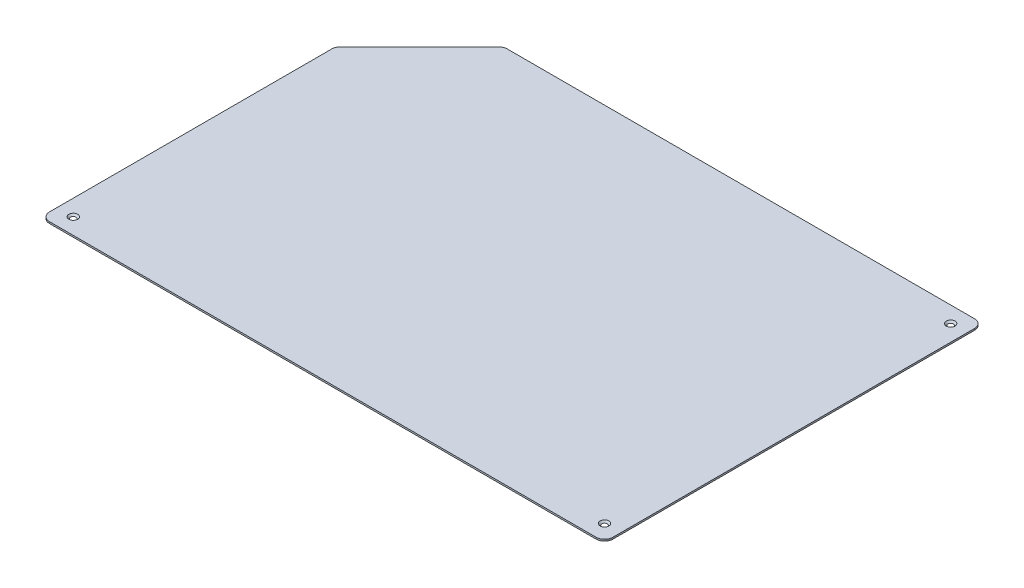
SolidWorks part; units mm, degrees
material "Alumina"
ref_plane "Front Plane" through (0, 0, 0) normal (0, 0, 1) x (1, 0, 0)
ref_plane "Top Plane" through (0, 0, 0) normal (0, 1, 0) x (1, 0, 0)
ref_plane "Right Plane" through (0, 0, 0) normal (1, 0, 0) x (0, 0, -1)
sketch "Sketch1" plane through (0, 0, 0) normal (0, 1, 0) x (1, 0, 0)
  line L1 (-300, -225) -> (300, -225)
  line L2 (-300, -225) -> (-300, 225) construction
  line L3 (-300, 225) -> (300, 225)
  line L4 (300, -225) -> (300, 225)
  line L5 (-300, -225) -> (300, 225) construction
  line L6 (-300, 225) -> (300, -225) construction
  line L7 (-370, -225) -> (-300, -225)
  line L8 (-370, -225) -> (-370, 225)
  line L9 (-370, 225) -> (-300, 225)
  line L10 (-300, -225) -> (-300, 225)
  line L11 (-370, -225) -> (-300, 225) construction
  line L12 (-370, 225) -> (-300, -225) construction
  point P0 (0, 0)
  point P6 (-335, 0)
  dimension "D1" = 450
  dimension "D2" = 600
  dimension "D3" = 70
extrude "Boss-Extrude1" add sketch "Sketch1" along normal blind 2 contours L7 L10 L9 L8 | L10 L1 L4 L3 region at (0, 0, 0) region at (-335, 0, 0)
sketch "Sketch2" plane through (0, 2, 0) normal (0, 1, 0) x (1, 0, 0)
  line L0 (-300, -225) -> (300, -225) construction
  line L1 (300, -225) -> (300, 225) construction
  line L2 (-300, 225) -> (300, 225) construction
  line L3 (-370, 225) -> (-300, 225) construction
  line L4 (-370, -225) -> (-370, 225) construction
  line L6 (-300, -225) -> (300, -225) construction
  line L7 (300, -225) -> (300, 225) construction
  line L8 (-300, 225) -> (300, 225) construction
  line L9 (-370, 225) -> (-300, 225) construction
  line L10 (-370, -225) -> (-370, 225) construction
  line L12 (-370, 225) -> (-350.8076, 205.8076) construction
  line L13 (-350.8076, 205.8076) -> (280.8076, 205.8076) construction
  line L14 (-350.8076, 205.8076) -> (-350.8076, -205.8076) construction
  line L15 (-350.8076, -205.8076) -> (280.8076, -205.8076) construction
  line L16 (280.8076, 205.8076) -> (280.8076, -205.8076) construction
  line L17 (280.8076, 205.8076) -> (300, 225) construction
  line L18 (280.8076, -205.8076) -> (300, -225) construction
  line L19 (-340.8076, 215.8076) -> (35014.5314, 35571.1467) construction
  line L20 (-35, 205.8076) -> (-35, -49794.1924) construction
  line L21 (0, 0) -> (50000, 0) construction
  line L22 (-331.6152, 186.6152) -> (35023.723, -35168.7247) construction
  line L23 (-270, 225) -> (-370, 125) construction
  circle A0 centre (-350.8076, 205.8076) radius 3 construction
  arc A1 (-370, 215) -> (-360, 225) centre (-360, 215) cw construction
  arc A2 (-341.6152, 186.6152) -> (-331.6152, 196.6152) centre (-341.6152, 196.6152) ccw construction
  arc A3 (271.6152, 186.6152) -> (261.6152, 196.6152) centre (271.6152, 196.6152) cw construction
  arc A4 (271.6152, -186.6152) -> (261.6152, -196.6152) centre (271.6152, -196.6152) ccw construction
  arc A5 (-341.6152, 186.6152) -> (-350.8076, 177.4228) centre (-341.6152, 177.4228) ccw construction
  arc A6 (-331.6152, 196.6152) -> (-322.4228, 205.8076) centre (-322.4228, 196.6152) cw construction
  arc A7 (271.6152, 186.6152) -> (280.8076, 177.4228) centre (271.6152, 177.4228) cw construction
  arc A8 (261.6152, 196.6152) -> (252.4228, 205.8076) centre (252.4228, 196.6152) ccw construction
  arc A9 (261.6152, -196.6152) -> (252.4228, -205.8076) centre (252.4228, -196.6152) cw construction
  arc A10 (271.6152, -186.6152) -> (280.8076, -177.4228) centre (271.6152, -177.4228) ccw construction
  circle A11 centre (-350.8076, 172.4767) radius 3 construction
  circle A13 centre (-317.4767, 205.8076) radius 3 construction
  arc A15 (-331.6152, -196.6152) -> (-322.4228, -205.8076) centre (-322.4228, -196.6152) ccw construction
  arc A16 (-341.6152, -186.6152) -> (-331.6152, -196.6152) centre (-341.6152, -196.6152) cw construction
  arc A17 (-341.6152, -186.6152) -> (-350.8076, -177.4228) centre (-341.6152, -177.4228) cw construction
  point P10 (-352.9289, 207.9289)
  point P16 (-367.0711, 222.0711)
  point P27 (-35, 205.8076)
  point P39 (-334.5442, 189.5442)
  point P53 (-350.8076, 175.4767)
  point P56 (-350.8076, 202.8076)
  dimension "D2" = 6
  dimension "D3" = 10
  dimension "D1" = 45
  dimension "D4" = 20
  dimension "D5" = 45
  dimension "D6" = 100
  dimension "D7" = 20
  dimension "D8" = 27.3309
sketch "Sketch6" plane through (0, 2, 0) normal (0, 1, 0) x (1, 0, 0)
  line L0 (280.8076, 177.4228) -> (280.8076, -177.4228) construction
  line L1 (-280, 205.8076) -> (252.4228, 205.8076) construction
  line L2 (-350.8076, 205.8076) -> (280.8076, 205.8076) construction
  line L5 (-350.8076, -205.8076) -> (280.8076, -205.8076) construction
  line L6 (-280, -205.8076) -> (252.4228, -205.8076) construction
  line L7 (-141752.968, 141607.9749) -> (176445.0758, -176590.0843) construction
  line L8 (-341.0607, 198.8891) -> (-332.7279, 190.5564)
  line L9 (-343.8891, 196.0607) -> (-341.0607, 198.8891) construction
  line L10 (-350.8076, 172.4767) -> (-317.4767, 205.8076) construction
  line L11 (-350.8076, 205.8076) -> (-334.1421, 189.1421) construction
  line L12 (-343.8891, 196.0607) -> (-335.5564, 187.7279)
  line L13 (-283.4499, 201.8076) -> (-67.3575, 201.8076) construction
  line L14 (-280, 205.8076) -> (-280, 201.8076)
  line L16 (-280, 224.1399) -> (-280, -49775.8601) construction
  line L17 (-300, -225) -> (-300, 225) construction
  line L18 (-300, -225) -> (-300, 225) construction
  arc A0 (271.6152, -186.6152) -> (280.8076, -177.4228) centre (271.6152, -177.4228) ccw construction
  arc A1 (271.6152, -186.6152) -> (261.6152, -196.6152) centre (271.6152, -196.6152) ccw construction
  arc A2 (252.4228, -205.8076) -> (261.6152, -196.6152) centre (252.4228, -196.6152) ccw construction
  arc A3 (280.8076, 177.4228) -> (271.6152, 186.6152) centre (271.6152, 177.4228) ccw construction
  arc A4 (261.6152, 196.6152) -> (271.6152, 186.6152) centre (271.6152, 196.6152) ccw construction
  arc A5 (261.6152, 196.6152) -> (252.4228, 205.8076) centre (252.4228, 196.6152) ccw construction
  arc A6 (271.6152, -186.6152) -> (280.8076, -177.4228) centre (271.6152, -177.4228) ccw construction
  arc A7 (271.6152, -186.6152) -> (261.6152, -196.6152) centre (271.6152, -196.6152) ccw construction
  arc A8 (252.4228, -205.8076) -> (261.6152, -196.6152) centre (252.4228, -196.6152) ccw construction
  arc A9 (280.8076, 177.4228) -> (271.6152, 186.6152) centre (271.6152, 177.4228) ccw construction
  arc A10 (261.6152, 196.6152) -> (271.6152, 186.6152) centre (271.6152, 196.6152) ccw construction
  arc A11 (261.6152, 196.6152) -> (252.4228, 205.8076) centre (252.4228, 196.6152) ccw construction
  arc A12 (-298.8275, 194.972) -> (-332.7279, 190.5564) centre (-317.4767, 205.8076) cw
  arc A13 (-335.5564, 187.7279) -> (-295.3689, 192.9625) centre (-317.4767, 205.8076) ccw
  arc A14 (-341.0607, 198.8891) -> (-343.8891, 196.0607) centre (-342.4749, 197.4749) ccw
  arc A15 (-298.8275, 194.972) -> (-280, 205.8076) centre (-280, 184.0329) cw
  arc A16 (-295.3689, 192.9625) -> (-280, 201.8076) centre (-280, 184.0329) cw
  point P31 (-342.4749, 197.4749)
  dimension "D1" = 4
  dimension "D2" = 20
extrude "Cut-Extrude1" cut sketch "Sketch6" against normal blind 1.5
hole_wizard "Tap Drill for M5x0.8 Tap2" positions "3DSketch4" profile "Sketch10" hole size "M5x0.8" standard "ANSI Metric" end condition through all
sketch3d "3DSketch4"
  point P0 (-350.8076, 2, 205.8076)
  point P3 (-350.8076, 2, -205.8076)
  point P6 (-317.4767, 2, -205.8076)
  point P9 (-350.8076, 2, -172.4767)
  point P12 (280.8076, 2, -205.8076)
  point P15 (280.8076, 2, 205.8076)
sketch "Sketch10" plane through (-350.8076, 2, 205.8076) normal (1, 0, 0) x (0, 0, 1)
  line L0 (0, 0) -> (0, 2)
  line L1 (0, 2) -> (2.1, 2)
  line L2 (2.1, 2) -> (2.1, 0)
  line L5 (2.1, 0) -> (0, 0)
  line L11 (0, -6.35) -> (0, 107.95) construction
  dimension "Thru Hole Dia." = 4.2
  dimension "Thru Hole Depth" = 2
sketch "Sketch11" plane through (0, 0, 225) normal (0, 0, 1) x (1, 0, 0)
  line L0 (-280, 2) -> (-298.8275, 2) construction
  line L1 (-280, 2) -> (-298.8275, 2) construction
  line L3 (-280, 2) -> (-280, 1.5)
  line L4 (-280, 2) -> (-278, 2)
  line L5 (-141762.1638, 2) -> (176435.8877, 2) construction
  line L6 (-278, 2) -> (-278, 1.5)
  line L7 (-270, 2) -> (-270, 1.5)
  line L8 (-270, 2) -> (-268, 2)
  line L9 (-268, 2) -> (-268, 1.5)
  line L10 (-260, 2) -> (-260, 1.5)
  line L11 (-260, 2) -> (-258, 2)
  line L12 (-258, 2) -> (-258, 1.5)
  line L13 (-250, 2) -> (-250, 1.5)
  line L14 (-250, 2) -> (-248, 2)
  line L15 (-248, 2) -> (-248, 1.5)
  line L16 (-240, 2) -> (-240, 1.5)
  line L17 (-240, 2) -> (-238, 2)
  line L18 (-238, 2) -> (-238, 1.5)
  line L19 (-230, 2) -> (-230, 1.5)
  line L20 (-230, 2) -> (-228, 2)
  line L21 (-228, 2) -> (-228, 1.5)
  line L22 (-220, 2) -> (-220, 1.5)
  line L23 (-220, 2) -> (-218, 2)
  line L24 (-218, 2) -> (-218, 1.5)
  line L25 (-210, 2) -> (-210, 1.5)
  line L26 (-210, 2) -> (-208, 2)
  line L27 (-208, 2) -> (-208, 1.5)
  line L28 (-200, 2) -> (-200, 1.5)
  line L29 (-200, 2) -> (-198, 2)
  line L30 (-198, 2) -> (-198, 1.5)
  line L31 (-190, 2) -> (-190, 1.5)
  line L32 (-190, 2) -> (-188, 2)
  line L33 (-188, 2) -> (-188, 1.5)
  line L34 (-180, 2) -> (-180, 1.5)
  line L35 (-180, 2) -> (-178, 2)
  line L36 (-178, 2) -> (-178, 1.5)
  line L37 (-170, 2) -> (-170, 1.5)
  line L38 (-170, 2) -> (-168, 2)
  line L39 (-168, 2) -> (-168, 1.5)
  line L40 (-160, 2) -> (-160, 1.5)
  line L41 (-160, 2) -> (-158, 2)
  line L42 (-158, 2) -> (-158, 1.5)
  line L43 (-150, 2) -> (-150, 1.5)
  line L44 (-150, 2) -> (-148, 2)
  line L45 (-148, 2) -> (-148, 1.5)
  line L46 (-140, 2) -> (-140, 1.5)
  line L47 (-140, 2) -> (-138, 2)
  line L48 (-138, 2) -> (-138, 1.5)
  line L49 (-130, 2) -> (-130, 1.5)
  line L50 (-130, 2) -> (-128, 2)
  line L51 (-128, 2) -> (-128, 1.5)
  line L52 (-120, 2) -> (-120, 1.5)
  line L53 (-120, 2) -> (-118, 2)
  line L54 (-118, 2) -> (-118, 1.5)
  line L55 (-110, 2) -> (-110, 1.5)
  line L56 (-110, 2) -> (-108, 2)
  line L57 (-108, 2) -> (-108, 1.5)
  line L58 (-100, 2) -> (-100, 1.5)
  line L59 (-100, 2) -> (-98, 2)
  line L60 (-98, 2) -> (-98, 1.5)
  line L61 (-90, 2) -> (-90, 1.5)
  line L62 (-90, 2) -> (-88, 2)
  line L63 (-88, 2) -> (-88, 1.5)
  line L64 (-80, 2) -> (-80, 1.5)
  line L65 (-80, 2) -> (-78, 2)
  line L66 (-78, 2) -> (-78, 1.5)
  line L67 (-70, 2) -> (-70, 1.5)
  line L68 (-70, 2) -> (-68, 2)
  line L69 (-68, 2) -> (-68, 1.5)
  line L70 (-60, 2) -> (-60, 1.5)
  line L71 (-60, 2) -> (-58, 2)
  line L72 (-58, 2) -> (-58, 1.5)
  line L73 (-50, 2) -> (-50, 1.5)
  line L74 (-50, 2) -> (-48, 2)
  line L75 (-48, 2) -> (-48, 1.5)
  line L76 (-40, 2) -> (-40, 1.5)
  line L77 (-40, 2) -> (-38, 2)
  line L78 (-38, 2) -> (-38, 1.5)
  line L79 (-30, 2) -> (-30, 1.5)
  line L80 (-30, 2) -> (-28, 2)
  line L81 (-28, 2) -> (-28, 1.5)
  line L82 (-20, 2) -> (-20, 1.5)
  line L83 (-20, 2) -> (-18, 2)
  line L84 (-18, 2) -> (-18, 1.5)
  line L85 (-10, 2) -> (-10, 1.5)
  line L86 (-10, 2) -> (-8, 2)
  line L87 (-8, 2) -> (-8, 1.5)
  line L88 (0, 2) -> (0, 1.5)
  line L89 (0, 2) -> (2, 2)
  line L90 (2, 2) -> (2, 1.5)
  line L91 (10, 2) -> (10, 1.5)
  line L92 (10, 2) -> (12, 2)
  line L93 (12, 2) -> (12, 1.5)
  line L94 (20, 2) -> (20, 1.5)
  line L95 (20, 2) -> (22, 2)
  line L96 (22, 2) -> (22, 1.5)
  line L97 (30, 2) -> (30, 1.5)
  line L98 (30, 2) -> (32, 2)
  line L99 (32, 2) -> (32, 1.5)
  line L100 (40, 2) -> (40, 1.5)
  line L101 (40, 2) -> (42, 2)
  line L102 (42, 2) -> (42, 1.5)
  line L103 (50, 2) -> (50, 1.5)
  line L104 (50, 2) -> (52, 2)
  line L105 (52, 2) -> (52, 1.5)
  line L106 (60, 2) -> (60, 1.5)
  line L107 (60, 2) -> (62, 2)
  line L108 (62, 2) -> (62, 1.5)
  line L109 (70, 2) -> (70, 1.5)
  line L110 (70, 2) -> (72, 2)
  line L111 (72, 2) -> (72, 1.5)
  line L112 (80, 2) -> (80, 1.5)
  line L113 (80, 2) -> (82, 2)
  line L114 (82, 2) -> (82, 1.5)
  line L115 (90, 2) -> (90, 1.5)
  line L116 (90, 2) -> (92, 2)
  line L117 (92, 2) -> (92, 1.5)
  line L118 (100, 2) -> (100, 1.5)
  line L119 (100, 2) -> (102, 2)
  line L120 (102, 2) -> (102, 1.5)
  line L121 (110, 2) -> (110, 1.5)
  line L122 (110, 2) -> (112, 2)
  line L123 (112, 2) -> (112, 1.5)
  line L124 (120, 2) -> (120, 1.5)
  line L125 (120, 2) -> (122, 2)
  line L126 (122, 2) -> (122, 1.5)
  line L127 (130, 2) -> (130, 1.5)
  line L128 (130, 2) -> (132, 2)
  line L129 (132, 2) -> (132, 1.5)
  line L130 (140, 2) -> (140, 1.5)
  line L131 (140, 2) -> (142, 2)
  line L132 (142, 2) -> (142, 1.5)
  line L133 (150, 2) -> (150, 1.5)
  line L134 (150, 2) -> (152, 2)
  line L135 (152, 2) -> (152, 1.5)
  line L136 (160, 2) -> (160, 1.5)
  line L137 (160, 2) -> (162, 2)
  line L138 (162, 2) -> (162, 1.5)
  line L139 (170, 2) -> (170, 1.5)
  line L140 (170, 2) -> (172, 2)
  line L141 (172, 2) -> (172, 1.5)
  line L142 (180, 2) -> (180, 1.5)
  line L143 (180, 2) -> (182, 2)
  line L144 (182, 2) -> (182, 1.5)
  line L145 (190, 2) -> (190, 1.5)
  line L146 (190, 2) -> (192, 2)
  line L147 (192, 2) -> (192, 1.5)
  line L148 (200, 2) -> (200, 1.5)
  line L149 (200, 2) -> (202, 2)
  line L150 (202, 2) -> (202, 1.5)
  line L151 (210, 2) -> (210, 1.5)
  line L152 (210, 2) -> (212, 2)
  line L153 (212, 2) -> (212, 1.5)
  line L154 (220, 2) -> (220, 1.5)
  line L155 (220, 2) -> (222, 2)
  line L156 (222, 2) -> (222, 1.5)
  line L157 (230, 2) -> (230, 1.5)
  line L158 (230, 2) -> (232, 2)
  line L159 (232, 2) -> (232, 1.5)
  line L160 (240, 2) -> (240, 1.5)
  line L161 (240, 2) -> (242, 2)
  line L162 (242, 2) -> (242, 1.5)
  line L163 (250, 2) -> (250, 1.5)
  line L164 (250, 2) -> (252, 2)
  line L165 (252, 2) -> (252, 1.5)
  line L166 (260, 2) -> (260, 1.5)
  line L167 (260, 2) -> (262, 2)
  line L168 (262, 2) -> (262, 1.5)
  line L169 (270, 2) -> (270, 1.5)
  line L170 (270, 2) -> (272, 2)
  line L171 (272, 2) -> (272, 1.5)
  line L172 (-280, 2) -> (-270, 2) construction
  line L173 (-300, 2) -> (300, 2) construction
  line L174 (-290, 2) -> (-290, 1.5)
  line L175 (-288, 2) -> (-288, 1.5)
  line L176 (-290, 2) -> (-288, 2)
  line L177 (-300, 2) -> (-300, 1.5)
  line L178 (-298, 2) -> (-298, 1.5)
  line L179 (-300, 2) -> (-298, 2)
  line L180 (-310, 2) -> (-310, 1.5)
  line L181 (-308, 2) -> (-308, 1.5)
  line L182 (-310, 2) -> (-308, 2)
  line L183 (-320, 2) -> (-320, 1.5)
  line L184 (-318, 2) -> (-318, 1.5)
  line L185 (-320, 2) -> (-318, 2)
  line L186 (-330, 2) -> (-330, 1.5)
  line L187 (-328, 2) -> (-328, 1.5)
  line L188 (-330, 2) -> (-328, 2)
  line L189 (-340, 2) -> (-340, 1.5)
  line L190 (-338, 2) -> (-338, 1.5)
  line L191 (-340, 2) -> (-338, 2)
  line L192 (-280, 1.5) -> (-290, 1.5) construction
  arc A0 (-280, 1.5) -> (-278, 1.5) centre (-279, 1.5) ccw
  arc A1 (-270, 1.5) -> (-268, 1.5) centre (-269, 1.5) ccw
  arc A2 (-260, 1.5) -> (-258, 1.5) centre (-259, 1.5) ccw
  arc A3 (-250, 1.5) -> (-248, 1.5) centre (-249, 1.5) ccw
  arc A4 (-240, 1.5) -> (-238, 1.5) centre (-239, 1.5) ccw
  arc A5 (-230, 1.5) -> (-228, 1.5) centre (-229, 1.5) ccw
  arc A6 (-220, 1.5) -> (-218, 1.5) centre (-219, 1.5) ccw
  arc A7 (-210, 1.5) -> (-208, 1.5) centre (-209, 1.5) ccw
  arc A8 (-200, 1.5) -> (-198, 1.5) centre (-199, 1.5) ccw
  arc A9 (-190, 1.5) -> (-188, 1.5) centre (-189, 1.5) ccw
  arc A10 (-180, 1.5) -> (-178, 1.5) centre (-179, 1.5) ccw
  arc A11 (-170, 1.5) -> (-168, 1.5) centre (-169, 1.5) ccw
  arc A12 (-160, 1.5) -> (-158, 1.5) centre (-159, 1.5) ccw
  arc A13 (-150, 1.5) -> (-148, 1.5) centre (-149, 1.5) ccw
  arc A14 (-140, 1.5) -> (-138, 1.5) centre (-139, 1.5) ccw
  arc A15 (-130, 1.5) -> (-128, 1.5) centre (-129, 1.5) ccw
  arc A16 (-120, 1.5) -> (-118, 1.5) centre (-119, 1.5) ccw
  arc A17 (-110, 1.5) -> (-108, 1.5) centre (-109, 1.5) ccw
  arc A18 (-100, 1.5) -> (-98, 1.5) centre (-99, 1.5) ccw
  arc A19 (-90, 1.5) -> (-88, 1.5) centre (-89, 1.5) ccw
  arc A20 (-80, 1.5) -> (-78, 1.5) centre (-79, 1.5) ccw
  arc A21 (-70, 1.5) -> (-68, 1.5) centre (-69, 1.5) ccw
  arc A22 (-60, 1.5) -> (-58, 1.5) centre (-59, 1.5) ccw
  arc A23 (-50, 1.5) -> (-48, 1.5) centre (-49, 1.5) ccw
  arc A24 (-40, 1.5) -> (-38, 1.5) centre (-39, 1.5) ccw
  arc A25 (-30, 1.5) -> (-28, 1.5) centre (-29, 1.5) ccw
  arc A26 (-20, 1.5) -> (-18, 1.5) centre (-19, 1.5) ccw
  arc A27 (-10, 1.5) -> (-8, 1.5) centre (-9, 1.5) ccw
  arc A28 (0, 1.5) -> (2, 1.5) centre (1, 1.5) ccw
  arc A29 (10, 1.5) -> (12, 1.5) centre (11, 1.5) ccw
  arc A30 (20, 1.5) -> (22, 1.5) centre (21, 1.5) ccw
  arc A31 (30, 1.5) -> (32, 1.5) centre (31, 1.5) ccw
  arc A32 (40, 1.5) -> (42, 1.5) centre (41, 1.5) ccw
  arc A33 (50, 1.5) -> (52, 1.5) centre (51, 1.5) ccw
  arc A34 (60, 1.5) -> (62, 1.5) centre (61, 1.5) ccw
  arc A35 (70, 1.5) -> (72, 1.5) centre (71, 1.5) ccw
  arc A36 (80, 1.5) -> (82, 1.5) centre (81, 1.5) ccw
  arc A37 (90, 1.5) -> (92, 1.5) centre (91, 1.5) ccw
  arc A38 (100, 1.5) -> (102, 1.5) centre (101, 1.5) ccw
  arc A39 (110, 1.5) -> (112, 1.5) centre (111, 1.5) ccw
  arc A40 (120, 1.5) -> (122, 1.5) centre (121, 1.5) ccw
  arc A41 (130, 1.5) -> (132, 1.5) centre (131, 1.5) ccw
  arc A42 (140, 1.5) -> (142, 1.5) centre (141, 1.5) ccw
  arc A43 (150, 1.5) -> (152, 1.5) centre (151, 1.5) ccw
  arc A44 (160, 1.5) -> (162, 1.5) centre (161, 1.5) ccw
  arc A45 (170, 1.5) -> (172, 1.5) centre (171, 1.5) ccw
  arc A46 (180, 1.5) -> (182, 1.5) centre (181, 1.5) ccw
  arc A47 (190, 1.5) -> (192, 1.5) centre (191, 1.5) ccw
  arc A48 (200, 1.5) -> (202, 1.5) centre (201, 1.5) ccw
  arc A49 (210, 1.5) -> (212, 1.5) centre (211, 1.5) ccw
  arc A50 (220, 1.5) -> (222, 1.5) centre (221, 1.5) ccw
  arc A51 (230, 1.5) -> (232, 1.5) centre (231, 1.5) ccw
  arc A52 (240, 1.5) -> (242, 1.5) centre (241, 1.5) ccw
  arc A53 (250, 1.5) -> (252, 1.5) centre (251, 1.5) ccw
  arc A54 (260, 1.5) -> (262, 1.5) centre (261, 1.5) ccw
  arc A55 (270, 1.5) -> (272, 1.5) centre (271, 1.5) ccw
  arc A56 (-290, 1.5) -> (-288, 1.5) centre (-289, 1.5) ccw
  arc A57 (-300, 1.5) -> (-298, 1.5) centre (-299, 1.5) ccw
  arc A58 (-310, 1.5) -> (-308, 1.5) centre (-309, 1.5) ccw
  arc A59 (-320, 1.5) -> (-318, 1.5) centre (-319, 1.5) ccw
  arc A60 (-330, 1.5) -> (-328, 1.5) centre (-329, 1.5) ccw
  arc A61 (-340, 1.5) -> (-338, 1.5) centre (-339, 1.5) ccw
  point P0 (-300, 2)
  dimension "D2" = 1
  dimension "D1" = 0.5
  dimension "D4" = 10
  dimension "D6" = 10
  dimension "D3" = 56
  dimension "D5" = 7
extrude "Cut-Extrude2" cut sketch "Sketch11" against normal offset from surface (410 mm away) 20 from offset 20 up to face at (-35, 1, -225) offset against normal yes
sketch "Sketch12" plane through (0, 2, 0) normal (0, 1, 0) x (1, 0, 0)
  line L0 (-280, 205.8076) -> (-315.3767, 205.8076)
  line L1 (-350.8076, 205.8076) -> (280.8076, 205.8076) construction
  line L2 (-350.8076, 205.8076) -> (-350.8076, -205.8076) construction
  line L3 (-350.8076, 202.8076) -> (-350.8076, 177.4228)
  line L4 (-350.8076, -177.4228) -> (-350.8076, -203.7076)
  line L5 (-332.7279, 190.5564) -> (-339, 196.8284)
  line L6 (-339, 196.8284) -> (-341.0607, 198.8891)
  line L7 (-343.8891, 196.0607) -> (-339, 191.1716)
  line L8 (-339, 191.1716) -> (-335.5564, 187.7279)
  line L9 (-280, 201.8076) -> (-280, 205.8076)
  line L10 (-332.7279, 190.5564) -> (-339, 196.8284)
  line L11 (-339, 196.8284) -> (-341.0607, 198.8891)
  line L12 (-343.8891, 196.0607) -> (-340, 192.1716)
  line L15 (-350.8076, -205.8076) -> (280.8076, -205.8076) construction
  line L16 (-348.7076, -205.8076) -> (-322.4228, -205.8076)
  line L17 (-35, -225) -> (-35, 49775) construction
  line L19 (-35, 200205.8076) -> (-35, -249794.1924) construction
  line L20 (0, 0) -> (-49761.8351, 0) construction
  line L22 (-200000, 0) -> (250000, 0) construction
  line L23 (278.7076, -205.8076) -> (252.4228, -205.8076)
  line L24 (280.8076, -177.4228) -> (280.8076, -203.7076)
  line L25 (280.8076, 177.4228) -> (280.8076, 203.7076)
  line L26 (278.7076, 205.8076) -> (252.4228, 205.8076)
  line L27 (-319.5767, 205.8076) -> (-347.8076, 205.8076)
  line L28 (-340, 192.1716) -> (-340, 186.7465)
  line L29 (-340, 192.1716) -> (-340, -205) construction
  arc A6 (-331.6152, -196.6152) -> (-322.4228, -205.8076) centre (-322.4228, -196.6152) ccw construction
  arc A7 (-331.6152, -196.6152) -> (-341.6152, -186.6152) centre (-341.6152, -196.6152) ccw construction
  arc A8 (-350.8076, -177.4228) -> (-341.6152, -186.6152) centre (-341.6152, -177.4228) ccw construction
  arc A9 (280.8076, -203.7076) -> (278.7076, -205.8076) centre (280.8076, -205.8076) ccw
  arc A10 (280.8076, -177.4228) -> (271.6152, -186.6152) centre (271.6152, -177.4228) cw
  arc A11 (261.6152, -196.6152) -> (271.6152, -186.6152) centre (271.6152, -196.6152) cw
  arc A12 (261.6152, -196.6152) -> (252.4228, -205.8076) centre (252.4228, -196.6152) cw
  arc A13 (261.6152, 196.6152) -> (252.4228, 205.8076) centre (252.4228, 196.6152) ccw
  arc A14 (261.6152, 196.6152) -> (271.6152, 186.6152) centre (271.6152, 196.6152) ccw
  arc A15 (-280, 205.8076) -> (-289, 203.8606) centre (-280, 184.0329) ccw
  arc A16 (-289, 203.8606) -> (-298.8275, 194.972) centre (-280, 184.0329) ccw
  arc A17 (-299, 194.6804) -> (-298.8275, 194.972) centre (-317.4767, 205.8076) ccw
  arc A18 (-309, 185.9746) -> (-299, 194.6804) centre (-317.4767, 205.8076) ccw
  arc A19 (-319, 184.2929) -> (-309, 185.9746) centre (-317.4767, 205.8076) ccw
  arc A20 (-329, 187.5754) -> (-319, 184.2929) centre (-317.4767, 205.8076) ccw
  arc A21 (-332.7279, 190.5564) -> (-329, 187.5754) centre (-317.4767, 205.8076) ccw
  arc A22 (-341.0607, 198.8891) -> (-343.8891, 196.0607) centre (-342.4749, 197.4749) ccw
  arc A23 (-335.5564, 187.7279) -> (-329, 182.983) centre (-317.4767, 205.8076) ccw
  arc A24 (-329, 182.983) -> (-319, 180.2845) centre (-317.4767, 205.8076) ccw
  arc A25 (-319, 180.2845) -> (-309, 181.6851) centre (-317.4767, 205.8076) ccw
  arc A26 (-309, 181.6851) -> (-299, 188.1338) centre (-317.4767, 205.8076) ccw
  arc A27 (-299, 188.1338) -> (-295.3689, 192.9625) centre (-317.4767, 205.8076) ccw
  arc A28 (-289, 199.3607) -> (-295.3689, 192.9625) centre (-280, 184.0329) ccw
  arc A29 (-280, 201.8076) -> (-289, 199.3607) centre (-280, 184.0329) ccw
  arc A30 (-280, 205.8076) -> (-289, 203.8606) centre (-280, 184.0329) ccw
  arc A31 (-289, 203.8606) -> (-298.8275, 194.972) centre (-280, 184.0329) ccw
  arc A32 (-299, 194.6804) -> (-298.8275, 194.972) centre (-317.4767, 205.8076) ccw
  arc A33 (-309, 185.9746) -> (-299, 194.6804) centre (-317.4767, 205.8076) ccw
  arc A34 (-319, 184.2929) -> (-309, 185.9746) centre (-317.4767, 205.8076) ccw
  arc A35 (-329, 187.5754) -> (-319, 184.2929) centre (-317.4767, 205.8076) ccw
  arc A36 (-332.7279, 190.5564) -> (-329, 187.5754) centre (-317.4767, 205.8076) ccw
  arc A37 (-341.0607, 198.8891) -> (-343.8891, 196.0607) centre (-342.4749, 197.4749) ccw
  arc A45 (-331.6152, -196.6152) -> (-322.4228, -205.8076) centre (-322.4228, -196.6152) ccw
  arc A46 (-331.6152, -196.6152) -> (-341.6152, -186.6152) centre (-341.6152, -196.6152) ccw
  arc A47 (-350.8076, -177.4228) -> (-341.6152, -186.6152) centre (-341.6152, -177.4228) ccw
  arc A48 (-347.8076, 205.8076) -> (-350.8076, 202.8076) centre (-350.8076, 205.8076) cw
  circle A49 centre (-350.8076, 205.8076) radius 3 construction
  arc A51 (-341.6152, 186.6152) -> (-331.6152, 196.6152) centre (-341.6152, 196.6152) ccw construction
  arc A52 (-341.6152, 186.6152) -> (-350.8076, 177.4228) centre (-341.6152, 177.4228) ccw construction
  circle A53 centre (-350.8076, -205.8076) radius 2.1 construction
  arc A54 (-341.6152, 186.6152) -> (-340, 186.7465) centre (-341.6152, 196.6152) ccw
  arc A55 (-341.6152, 186.6152) -> (-350.8076, 177.4228) centre (-341.6152, 177.4228) ccw
  arc A56 (-350.8076, -203.7076) -> (-348.7076, -205.8076) centre (-350.8076, -205.8076) cw
  arc A57 (280.8076, 177.4228) -> (271.6152, 186.6152) centre (271.6152, 177.4228) ccw
  arc A58 (280.8076, 203.7076) -> (278.7076, 205.8076) centre (280.8076, 205.8076) cw
  arc A59 (-319.5767, 205.8076) -> (-315.3767, 205.8076) centre (-317.4767, 205.8076) ccw
  arc A60 (-318, 203.7739) -> (-319.4152, 205) centre (-317.4767, 205.8076) ccw construction
  dimension "D1" = 0
extrude "Boss-Extrude2" add sketch "Sketch12" against normal up to surface (1.5 mm away) up to face at (-313.8725, 0.5, -192.2606)
sketch "Sketch13" plane through (-280, 0, 0) normal (-1, 0, 0) x (0, 0, 1)
  line L0 (-205, 2) -> (-205.8076, 2) construction
  line L1 (-205.8076, 0.5) -> (-201.8076, 0.5)
  line L2 (-205.8076, 0.5) -> (-205.8076, 2)
  line L3 (-205.8076, 2) -> (-201.8076, 2)
  line L4 (-201.8076, 0.5) -> (-201.8076, 2)
  line L5 (-201.8076, 0.5) -> (-201.8076, 1.5) construction
extrude "Cut-Extrude3" cut sketch "Sketch13" against normal up to surface (532 mm away) up to face at (252, 1.75, 0)
sketch "Sketch14" plane through (0, 2, 0) normal (0, 1, 0) x (1, 0, 0)
  line L0 (252.4228, 205.8076) -> (252, 205.8076)
  line L1 (252, 205.8076) -> (252, 201.8076)
  line L2 (252, 205.8076) -> (252, -205) construction
  line L3 (252, 205.8076) -> (252, 201.8076) construction
  line L4 (251, 201.8076) -> (241, 201.8076) construction
  line L6 (272, 186.6072) -> (272, 182.6182)
  line L7 (272, 186.6072) -> (272, -186.6072) construction
  arc A0 (280.8076, 177.4228) -> (271.6152, 186.6152) centre (271.6152, 177.4228) ccw construction
  arc A1 (261.6152, 196.6152) -> (271.6152, 186.6152) centre (271.6152, 196.6152) ccw construction
  arc A2 (261.6152, 196.6152) -> (252.4228, 205.8076) centre (252.4228, 196.6152) ccw construction
  arc A3 (272, 186.6072) -> (271.6152, 186.6152) centre (271.6152, 177.4228) ccw
  arc A4 (261.6152, 196.6152) -> (271.6152, 186.6152) centre (271.6152, 196.6152) ccw
  arc A5 (261.6152, 196.6152) -> (252.4228, 205.8076) centre (252.4228, 196.6152) ccw
  arc A6 (252, 201.8076) -> (257.6324, 196.6152) centre (252.4228, 196.6152) cw
  arc A7 (257.6324, 196.6152) -> (271.6152, 182.6324) centre (271.6152, 196.6152) ccw
  arc A8 (271.6152, 182.6324) -> (272, 182.6182) centre (271.6152, 177.4228) cw
extrude "Cut-Extrude4" cut sketch "Sketch14" against normal up to surface (1.5 mm away) up to face at (-66.3645, 0.5, -199.8894)
fillet "Fillet1" radius 10 4 edges at (-370, 1, -225) (300, 1, -225) (300, 1, 225) (-370, 1, 225)
mirror "Mirror1" about plane through (0, 0, 0) normal (0, 1, 0) of bodies 108
delete or keep bodies "Body-Delete/Keep 1" type delete bodies bodies 108
sketch "Sketch15" plane through (0, 0, 0) normal (0, 1, 0) x (1, 0, 0)
  line L0 (-270, 225) -> (-370, 125) construction
  line L1 (-270, 225) -> (-370, 125)
  line L2 (-360, 225) -> (290, 225) construction
  line L3 (-370, -215) -> (-370, 215) construction
  line L4 (-360, 225) -> (-270, 225)
  line L5 (-370, 125) -> (-370, 215)
  arc A0 (-360, 225) -> (-370, 215) centre (-360, 215) ccw construction
  arc A1 (-360, 225) -> (-370, 215) centre (-360, 215) ccw
extrude "Cut-Extrude5" cut sketch "Sketch15" against normal through all
fillet "Fillet2" radius 10 2 edges at (-370, -1, -125) (-270, -1, -225)
sketch "Sketch17" plane through (0, 0, 0) normal (0, 1, 0) x (1, 0, 0)
  circle A0 centre (-350.8076, -205.8076) radius 2.1 construction
  circle A1 centre (280.8076, 205.8076) radius 2.1 construction
  circle A2 centre (280.8076, -205.8076) radius 2.1 construction
  circle A3 centre (-350.8076, -205.8076) radius 2.1 construction
  circle A4 centre (280.8076, 205.8076) radius 2.1 construction
  circle A5 centre (280.8076, -205.8076) radius 2.1 construction
hole_wizard "CSK for M5 Flat Head Machine Screw1" positions "3DSketch6" profile "Sketch19" countersink size "M5" standard "ANSI Metric" end condition through all
sketch3d "3DSketch6"
  point P0 (280.8076, 0, -205.8076)
  point P3 (280.8076, 0, 205.8076)
  point P6 (-350.8076, 0, 205.8076)
sketch "Sketch19" plane through (280.8076, 0, -205.8076) normal (1, 0, 0) x (0, 0, 1)
  line L0 (0, 0) -> (0, 2)
  line L1 (0, 2) -> (2.75, 2)
  line L2 (2.75, 2) -> (2.75, 2.45)
  line L3 (2.75, 2.45) -> (5.2, 0)
  line L5 (5.2, 0) -> (0, 0)
  line L6 (-2.75, 2.45) -> (-5.2, 0) construction
  line L11 (0, -6.35) -> (0, 107.95) construction
  dimension "Thru Hole Dia." = 5.5
  dimension "Thru Hole Depth" = 2
  dimension "Near C'Sink Dia." = 10.4
  dimension "Near C'Sink Angle" = 90
equation "\"half_plate_thickness\" = 0.2cm'Total plate thickness: 1 cm"
equation "\"plate_length\"= 60cm'Parallel to x-axis"
equation "\"plate_width\"= 45cm'Parallel to z-axis"
equation "\"electronics_box_length\"= 10cm'Parallel to x-axis"
equation "\"wall_width\"= 2cm'Same value for wall_length"
equation "\"eds_radius\"= 1mm"
equation "\"eds_spacing\"= 10mm"
equation "\"general_tolerance\"= 0.5mm"
equation "\"eds_count\"= 57"
equation "\"plate_fillet_radius\"= 10mm"
equation "\"tooth_height\"= 1cm"
equation "\"tooth_offset\"= 0.5cm"
equation "\"tooth_patch_width\"= 7.5cm"
equation "\"D1@Sketch1\"=\"plate_width\""
equation "\"D2@Sketch1\"=\"plate_length\""
equation "\"D3@Sketch1\"=\"electronics_box_length\"-3cm"
equation "\"D1@Boss-Extrude1\"=\"half_plate_thickness\""
equation "\"D3@Sketch2\"=\"plate_fillet_radius\""
equation "\"D4@Sketch2\"=\"wall_width\""
equation "\"D6@Sketch2\"=\"electronics_box_length\""
equation "\"D7@Sketch2\"=\"wall_width\""
equation "\"D1@Sketch6\"=\"eds_radius\"*4"
equation "\"D1@Cut-Extrude1\"=\"eds_radius\"+\"general_tolerance\""
equation "\"D2@Sketch6\"=\"wall_width\""
equation "\"D1@Sketch11\"=\"general_tolerance\""
equation "\"D2@Sketch11\"=\"eds_radius\""
equation "\"D4@Sketch11\"=\"eds_spacing\""
equation "\"D6@Sketch11\"=\"eds_spacing\""
equation "\"D19@Cut-Extrude2\"=\"wall_width\""
equation "\"D1@Cut-Extrude2\"=\"wall_width\""
equation "\"D1@Fillet1\"=\"plate_fillet_radius\""
equation "\"D1@Fillet2\"=\"plate_fillet_radius\""
